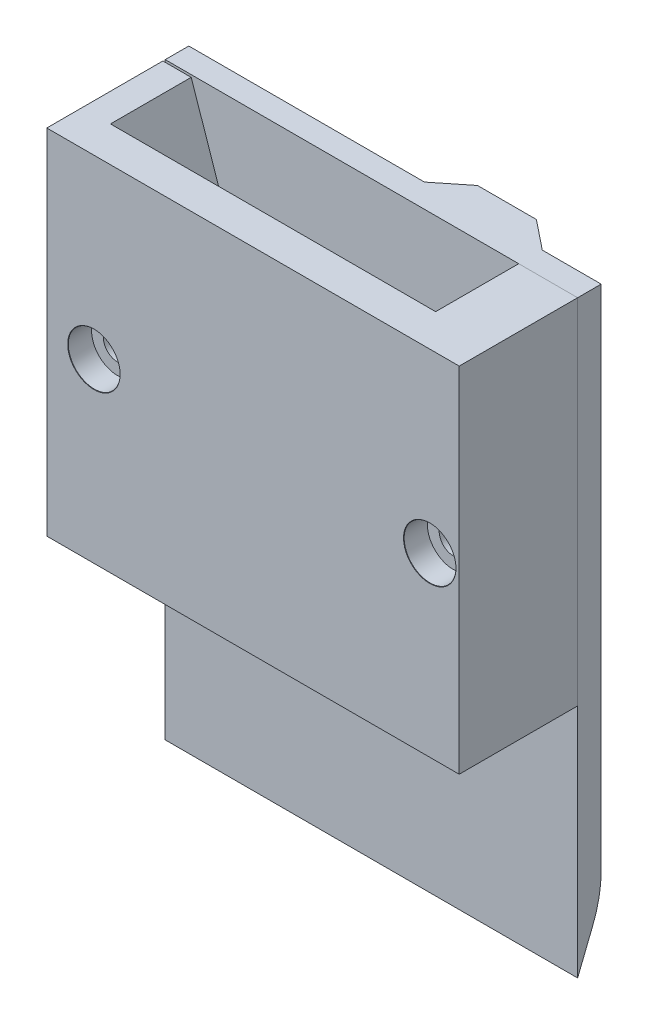
SolidWorks part; units mm, degrees
note: The reader was unsure of these and kept them because the rebuilt part matched: shared geometry of "Sketch1<4>".
ref_plane "Front Plane" through (0, 0, 0) normal (0, 0, 1) x (1, 0, 0)
ref_plane "Top Plane" through (0, 0, 0) normal (0, 1, 0) x (1, 0, 0)
ref_plane "Right Plane" through (0, 0, 0) normal (1, 0, 0) x (0, 0, -1)
sketch "Sketch1" plane through (0, 0, 1400.1446) normal (0, 0, 1) x (1, 0, 0)
  line L1 (732.96, 768.9401) -> (767.96, 768.9401)
  line L2 (732.96, 768.9401) -> (732.96, 748.9401)
  line L3 (732.96, 748.9401) -> (767.96, 748.9401)
  line L4 (767.96, 768.9401) -> (767.96, 748.9401)
  line L17 (736.7247, 794.9401) -> (762.96, 794.9401)
  line L18 (762.96, 794.9401) -> (762.96, 769.9401)
  line L19 (743.2992, 775.6153) -> (718.9107, 847.3018)
  line L20 (717.7107, 757.5452) -> (742.0991, 772.3186)
  line L21 (743.2992, 775.6153) -> (736.7247, 794.9401)
  line L22 (738.1726, 769.9401) -> (742.0991, 772.3186)
  line L23 (762.96, 769.9401) -> (738.1726, 769.9401)
  line L24 (762.76, 714.0209) -> (762.76, 1214.0209) construction
  line L25 (767.96, 768.9401) -> (767.96, 798.9401)
  line L26 (767.96, 798.9401) -> (732.96, 798.9401)
  line L27 (732.96, 798.9401) -> (732.96, 768.9401)
  line L28 (732.96, 768.9401) -> (767.96, 768.9401)
  line L29 (736.7247, 794.9401) -> (735.3639, 798.9401)
  line L30 (738.1726, 769.9401) -> (736.5217, 768.9401)
  arc A6 (714.7056, 757.3741) -> (717.8143, 757.3741) centre (716.26, 759.9401) ccw construction
  arc A7 (742.0991, 772.3186) -> (743.2992, 775.6153) centre (740.6484, 774.7135) ccw
  arc A8 (742.0991, 772.3186) -> (743.2992, 775.6153) centre (740.6484, 774.7135) ccw
  dimension "D2" = 0.2
  dimension "D3" = 10
  dimension "D4" = 5
  dimension "D5" = 4
  dimension "D6" = 1
  dimension "D7" = 30
  dimension "D8" = 35
  dimension "D9" = 20
  dimension "D1" = 0.2
extrude "Boss-Extrude2" add sketch "Sketch1" against normal blind 2 from offset 0.2 contours L22 A8 L21 L17 L18 L23 | L30 L23 L18 L17 L29 L26 L25 L28 L27 | A8 L22 L30 L27 L26 L29 L21 | L1 L28 L4 L3 L2 offset against normal yes
extrude "Boss-Extrude3" add sketch "Sketch1<4>" along normal blind 6.85 separate body contours A8 L22 L30 L27 L26 L29 L21
sketch "Sketch1<4>" plane through (0, 0, 1400.1446) normal (0, 0, 1) x (1, 0, 0) same geometry as "Sketch1"
sketch "Sketch2" plane through (0, 748.9401, 0) normal (0, -1, 0) x (1, 0, 0)
  line L0 (752.96, 1397.9446) -> (755.46, 1395.9446)
  line L2 (755.46, 1395.9446) -> (760.46, 1395.9446)
  line L3 (760.46, 1395.9446) -> (762.96, 1397.9446)
  line L4 (762.96, 1397.9446) -> (752.96, 1397.9446)
  line L7 (732.96, 1399.9446) -> (767.96, 1399.9446) construction
  line L8 (767.96, 1397.9446) -> (767.96, 1399.9446) construction
  line L9 (732.96, 1397.9446) -> (767.96, 1397.9446) construction
  point P2 (752.96, 1397.9446)
  point P9 (764.9929, 1398.3446)
  dimension "D1" = 4
  dimension "D2" = 10
  dimension "D3" = 5
  dimension "D4" = 5
extrude "Boss-Extrude4" add sketch "Sketch2" against normal up to surface (50 mm away) up to face at (750.46, 798.9401, 1398.9446)
sketch "Sketch3" plane through (0, 0, 1406.9946) normal (0, 0, 1) x (1, 0, 0)
  line L1 (732.96, 798.9401) -> (767.96, 798.9401)
  line L2 (732.96, 798.9401) -> (732.96, 768.9401)
  line L3 (732.96, 768.9401) -> (767.96, 768.9401)
  line L4 (767.96, 798.9401) -> (767.96, 768.9401)
extrude "Boss-Extrude5" add sketch "Sketch3" along normal blind 3
sketch "Sketch4" plane through (0, 0, 1406.9946) normal (0, 0, -1) x (-1, 0, 0)
  line L0 (-732.96, 768.9401) -> (-767.96, 768.9401) construction
  line L1 (-767.96, 798.9401) -> (-762.96, 798.9401)
  line L2 (-767.96, 798.9401) -> (-767.96, 768.9401)
  line L3 (-767.96, 768.9401) -> (-762.96, 768.9401)
  line L4 (-762.96, 798.9401) -> (-762.96, 768.9401)
  line L5 (-762.76, 714.0209) -> (-762.76, 1214.0209) construction
  dimension "D1" = 0.2
extrude "Boss-Extrude6" add sketch "Sketch4" along normal up to surface (7.05 mm away)
sketch "Sketch5" plane through (0, 0, 1409.9946) normal (0, 0, 1) x (1, 0, 0)
  line L0 (767.96, 768.9401) -> (767.96, 798.9401) construction
  line L1 (767.96, 783.9401) -> (762.96, 783.9401) construction
  line L2 (762.96, 794.9401) -> (762.96, 769.9401) construction
  line L3 (732.96, 798.9401) -> (732.96, 768.9401) construction
  point P0 (736.96, 783.9401)
  point P1 (765.46, 783.9401)
  point P4 (767.96, 783.9401)
  point P9 (765.46, 783.9401)
  dimension "D1" = 4
hole_wizard "CBORE for M2 SHCS1" positions "Sketch5" profile "Sketch6" counterbore size "M2" standard "ANSI Metric" end condition through all
sketch "Sketch6" plane through (736.96, 783.9401, 1409.9946) normal (1, 0, 0) x (0, -1, 0)
  line L0 (0, 0) -> (0, 14.05)
  line L1 (0, 14.05) -> (1.2, 14.05)
  line L3 (1.2, 14.05) -> (1.2, 2)
  line L4 (2.2, 2) -> (1.2, 2)
  line L5 (2.2, 2) -> (2.2, 0.025)
  line L6 (2.2, 0.025) -> (2.225, 0)
  line L7 (2.225, 0) -> (0, 0)
  line L8 (-2.2, 0.025) -> (-2.225, 0) construction
  line L11 (0, -6.35) -> (0, 107.95) construction
  dimension "Thru Hole Dia." = 2.4
  dimension "Thru Hole Depth" = 14.05
  dimension "C'Bore Dia." = 4.4
  dimension "C'Bore Depth" = 2
  dimension "Near C'Sink Dia." = 4.45
  dimension "Near C'Sink Angle" = 90
sketch "Sketch7" plane through (0, 0, 1397.9446) normal (0, 0, -1) x (-1, 0, 0)
  line L1 (-763.36, 785.1525) -> (-765.46, 786.3649)
  line L2 (-765.46, 786.3649) -> (-767.56, 785.1525)
  line L3 (-767.56, 785.1525) -> (-767.56, 782.7276)
  line L4 (-767.56, 782.7276) -> (-765.46, 781.5152)
  line L5 (-765.46, 781.5152) -> (-763.36, 782.7276)
  line L6 (-763.36, 782.7276) -> (-763.36, 785.1525)
  line L7 (-734.86, 785.1525) -> (-736.96, 786.3649)
  line L8 (-736.96, 786.3649) -> (-739.06, 785.1525)
  line L9 (-739.06, 785.1525) -> (-739.06, 782.7276)
  line L10 (-739.06, 782.7276) -> (-736.96, 781.5152)
  line L11 (-736.96, 781.5152) -> (-734.86, 782.7276)
  line L12 (-734.86, 782.7276) -> (-734.86, 785.1525)
  circle A0 centre (-765.46, 783.9401) radius 2.1 construction
  circle A1 centre (-736.96, 783.9401) radius 2.1 construction
  dimension "D1" = 4.2
extrude "Cut-Extrude1" cut sketch "Sketch7" against normal blind 1
sketch "Sketch8" plane through (767.96, 0, 0) normal (1, 0, 0) x (0, 0, -1)
  line L0 (-1399.9446, 748.9401) -> (-1395.9446, 758.9401)
  line L1 (-1395.9446, 798.9401) -> (-1395.9446, 748.9401) construction
  line L2 (-1395.9446, 758.9401) -> (-1395.9446, 748.9401)
  line L3 (-1395.9446, 748.9401) -> (-1397.9446, 748.9401) construction
  line L4 (-1395.9446, 748.9401) -> (-1399.9446, 748.9401)
  line L5 (-1399.9446, 748.9401) -> (-1399.9446, 798.9401) construction
  line L6 (-1397.9446, 748.9401) -> (-1399.9446, 748.9401) construction
  point P8 (-1395.9446, 768.9401)
  point P9 (0, 0)
  point P10 (-1395.9446, 738.9401)
  point P11 (-1399.9446, 748.9401)
  dimension "D1" = 10
extrude "Cut-Extrude2" cut sketch "Sketch8" against normal through all
fillet "Fillet1" radius 10 3 edges at (765.46, 753.9401, 1397.9446) (742.96, 753.9401, 1397.9446) (757.96, 758.9401, 1395.9446)
